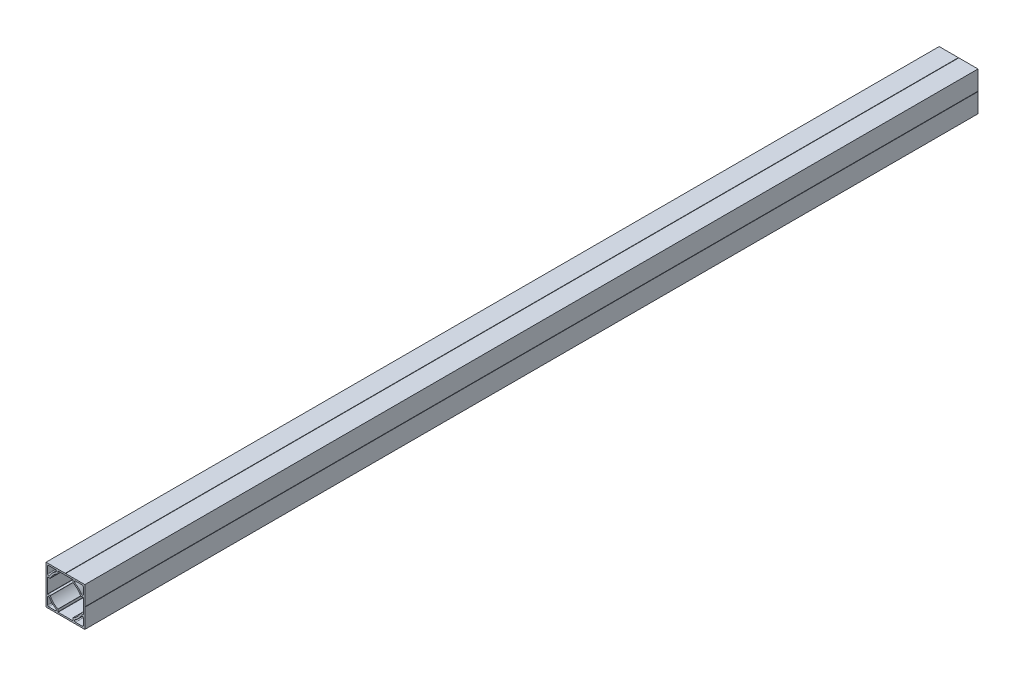
SolidWorks part; units mm, degrees
material "6061 Alloy"
ref_plane "Front Plane" through (0, 0, 0) normal (0, 0, 1) x (1, 0, 0)
ref_plane "Top Plane" through (0, 0, 0) normal (0, 1, 0) x (1, 0, 0)
ref_plane "Right Plane" through (0, 0, 0) normal (1, 0, 0) x (0, 0, -1)
other "Configuration Table"
sketch "Sketch1" plane through (0, 0, 0) normal (0, 0, 1) x (1, 0, 0)
  line L6 (1.7076, 1.016) -> (6.1029, 1.016)
  line L7 (1.016, 6.1029) -> (1.016, 1.7076)
  line L10 (25.4, 12.827) -> (25.4, 25.4)
  line L11 (25.4, 25.4) -> (12.827, 25.4)
  line L14 (12.573, 25.4) -> (0, 25.4)
  line L15 (0, 25.4) -> (0, 12.827)
  line L16 (0, 12.827) -> (0.127, 12.7)
  line L17 (0.127, 12.7) -> (0, 12.573)
  line L18 (0, 12.573) -> (0, 0)
  line L22 (12.827, 0) -> (25.4, 0)
  line L23 (25.4, 0) -> (25.4, 12.573)
  line L24 (1.143, 7.8105) -> (2.6421, 7.8105)
  line L25 (1.016, 17.4625) -> (1.016, 7.9375)
  line L26 (2.6421, 17.5895) -> (1.143, 17.5895)
  line L27 (1.016, 23.6924) -> (1.016, 19.2971)
  line L28 (6.1029, 24.384) -> (1.7076, 24.384)
  line L29 (17.5895, 22.7579) -> (17.5895, 24.257)
  line L30 (17.4625, 24.384) -> (7.9375, 24.384)
  line L31 (7.8105, 24.257) -> (7.8105, 22.7579)
  line L32 (23.6924, 24.384) -> (19.2971, 24.384)
  line L33 (24.384, 19.2971) -> (24.384, 23.6924)
  line L34 (22.7579, 7.8105) -> (24.257, 7.8105)
  line L35 (24.384, 7.9375) -> (24.384, 17.4625)
  line L36 (24.257, 17.5895) -> (22.7579, 17.5895)
  line L37 (24.384, 1.7076) -> (24.384, 6.1029)
  line L38 (19.2971, 1.016) -> (23.6924, 1.016)
  line L39 (7.8105, 2.6421) -> (7.8105, 1.143)
  line L40 (7.9375, 1.016) -> (17.4625, 1.016)
  line L41 (17.5895, 1.143) -> (17.5895, 2.6421)
  line L44 (12.827, 25.4) -> (12.7, 25.273)
  line L45 (12.7, 25.273) -> (12.573, 25.4)
  line L46 (25.4, 12.573) -> (25.273, 12.7)
  line L47 (25.273, 12.7) -> (25.4, 12.827)
  line L48 (12.573, 0) -> (12.7, 0.127)
  line L49 (12.7, 0.127) -> (12.827, 0)
  line L50 (12.573, 0) -> (0, 0)
  arc A14 (1.016, 1.7076) -> (1.7076, 1.016) centre (1.7076, 1.7076) ccw
  arc A15 (2.3006, 6.4588) -> (1.016, 6.1029) centre (1.7076, 6.1029) ccw
  arc A16 (2.3006, 6.4588) -> (6.4588, 2.3006) centre (12.7, 12.7) ccw
  arc A17 (6.1029, 1.016) -> (6.4588, 2.3006) centre (6.1029, 1.7076) ccw
  arc A18 (2.7558, 7.7402) -> (7.7402, 2.7558) centre (12.7, 12.7) ccw
  arc A19 (2.7558, 7.7402) -> (2.6421, 7.8105) centre (2.6421, 7.6835) ccw
  arc A20 (1.016, 7.9375) -> (1.143, 7.8105) centre (1.143, 7.9375) ccw
  arc A21 (1.143, 17.5895) -> (1.016, 17.4625) centre (1.143, 17.4625) ccw
  arc A22 (2.6421, 17.5895) -> (2.7558, 17.6598) centre (2.6421, 17.7165) ccw
  arc A23 (1.016, 19.2971) -> (2.3006, 18.9412) centre (1.7076, 19.2971) ccw
  arc A24 (6.4588, 23.0994) -> (2.3006, 18.9412) centre (12.7, 12.7) ccw
  arc A25 (6.4588, 23.0994) -> (6.1029, 24.384) centre (6.1029, 23.6924) ccw
  arc A26 (1.7076, 24.384) -> (1.016, 23.6924) centre (1.7076, 23.6924) ccw
  arc A27 (17.5895, 24.257) -> (17.4625, 24.384) centre (17.4625, 24.257) ccw
  arc A28 (17.5895, 22.7579) -> (17.6598, 22.6442) centre (17.7165, 22.7579) ccw
  arc A29 (7.9375, 24.384) -> (7.8105, 24.257) centre (7.9375, 24.257) ccw
  arc A30 (7.7402, 22.6442) -> (7.8105, 22.7579) centre (7.6835, 22.7579) ccw
  arc A31 (7.7402, 22.6442) -> (2.7558, 17.6598) centre (12.7, 12.7) ccw
  arc A32 (19.2971, 24.384) -> (18.9412, 23.0994) centre (19.2971, 23.6924) ccw
  arc A33 (23.0994, 18.9412) -> (18.9412, 23.0994) centre (12.7, 12.7) ccw
  arc A34 (23.0994, 18.9412) -> (24.384, 19.2971) centre (23.6924, 19.2971) ccw
  arc A35 (24.384, 23.6924) -> (23.6924, 24.384) centre (23.6924, 23.6924) ccw
  arc A36 (24.257, 7.8105) -> (24.384, 7.9375) centre (24.257, 7.9375) ccw
  arc A37 (22.7579, 7.8105) -> (22.6442, 7.7402) centre (22.7579, 7.6835) ccw
  arc A38 (24.384, 17.4625) -> (24.257, 17.5895) centre (24.257, 17.4625) ccw
  arc A39 (22.6442, 17.6598) -> (22.7579, 17.5895) centre (22.7579, 17.7165) ccw
  arc A40 (22.6442, 17.6598) -> (17.6598, 22.6442) centre (12.7, 12.7) ccw
  arc A41 (24.384, 6.1029) -> (23.0994, 6.4588) centre (23.6924, 6.1029) ccw
  arc A42 (18.9412, 2.3006) -> (23.0994, 6.4588) centre (12.7, 12.7) ccw
  arc A43 (18.9412, 2.3006) -> (19.2971, 1.016) centre (19.2971, 1.7076) ccw
  arc A44 (23.6924, 1.016) -> (24.384, 1.7076) centre (23.6924, 1.7076) ccw
  arc A45 (7.8105, 1.143) -> (7.9375, 1.016) centre (7.9375, 1.143) ccw
  arc A46 (7.8105, 2.6421) -> (7.7402, 2.7558) centre (7.6835, 2.6421) ccw
  arc A47 (17.4625, 1.016) -> (17.5895, 1.143) centre (17.4625, 1.143) ccw
  arc A48 (17.6598, 2.7558) -> (17.5895, 2.6421) centre (17.7165, 2.6421) ccw
  arc A49 (17.6598, 2.7558) -> (22.6442, 7.7402) centre (12.7, 12.7) ccw
  point P41 (12.7, 24.384)
  point P109 (12.7, 12.7)
  point P116 (12.7, 12.7)
  dimension "D1" = 25.4
  dimension "D2" = 1.016
  dimension "D3" = 4
  dimension "D4" = 1.016
  dimension "D7" = 0.127
  dimension "D12" = 11.1125
  dimension "D5" = 0.127
  dimension "D13" = 12.1285
  dimension "D6" = 9.525
  dimension "D8" = 135
  dimension "D9" = 5.7785
  dimension "D10" = 0.127
  dimension "D11" = 4
extrude "Boss-Extrude1" add sketch "Sketch1" along normal blind 584.2
sketch "Sketch2" [suppressed] plane through (0, 0, 0) normal (-1, 0, 0) x (0, 0, 1)
  line L0 (1193.8, 12.7) -> (0, 12.7) construction
  line L1 (0, 12.573) -> (0, 0) construction
  circle A0 centre (12.7, 12.7) radius 2.54
  dimension "D1" = 5.08
  dimension "D2" = 12.7
extrude "Cut-Extrude1" [suppressed] cut sketch "Sketch2" against normal through all
pattern_circular "CirPattern1" [suppressed] count 4 over 360 reverse direction yes of bodies 102
pattern_linear "LPattern1" [suppressed] count 95 spacing 12.7 of bodies 103
equation "\"Length\" = 23"
equation "\"D1@Boss-Extrude1\"=\"Length\""
